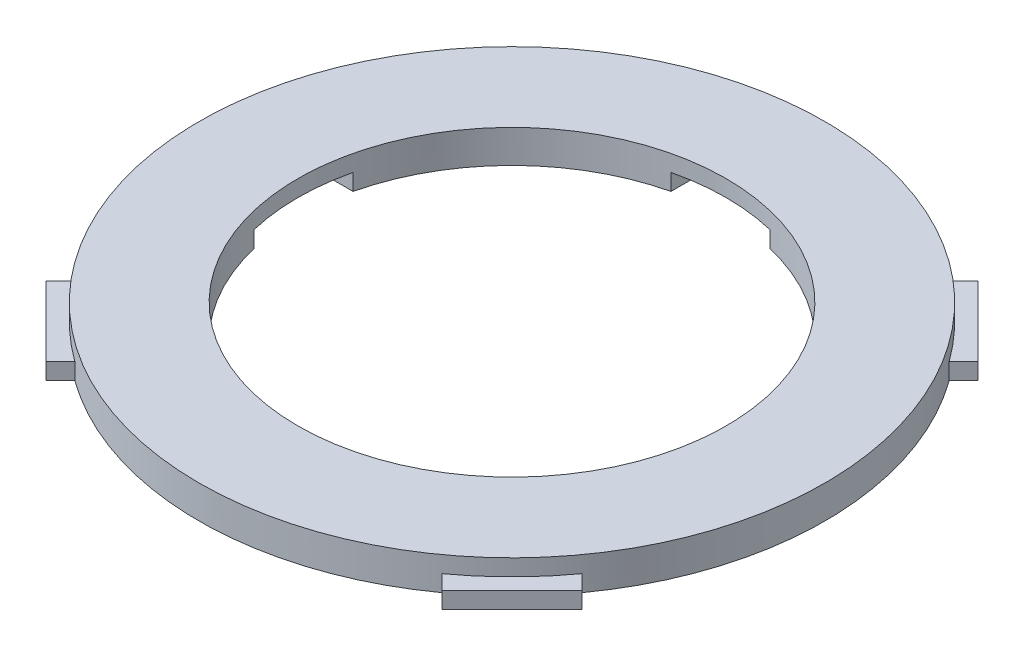
SolidWorks part; units mm, degrees
ref_plane "Front Plane" through (0, 0, 0) normal (0, 0, 1) x (1, 0, 0)
ref_plane "Top Plane" through (0, 0, 0) normal (0, 1, 0) x (1, 0, 0)
ref_plane "Right Plane" through (0, 0, 0) normal (1, 0, 0) x (0, 0, -1)
sketch "Sketch1" plane through (0, 0, 0) normal (0, 1, 0) x (1, 0, 0)
  line L0 (-67.1751, -67.1751) -> (67.1751, 67.1751) construction
  line L1 (-95, 0) -> (95, 0) construction
  line L2 (-67.1751, 67.1751) -> (67.1751, -67.1751) construction
  line L3 (0, 95) -> (0, -95) construction
  line L4 (67.1751, 67.1751) -> (-67.1751, -67.1751) construction
  line L5 (95, 0) -> (-95, 0) construction
  line L6 (67.1751, -67.1751) -> (-67.1751, 67.1751) construction
  line L7 (0, -95) -> (0, 95) construction
  line L8 (67.1751, 67.1751) -> (70.7107, 70.7107) construction
  line L9 (60.1041, 81.3173) -> (81.3173, 60.1041)
  line L10 (60.1041, 81.3173) -> (55.7259, 76.9391)
  line L11 (81.3173, 60.1041) -> (76.9391, 55.7259)
  line L12 (81.3173, -60.1041) -> (76.9391, -55.7259)
  line L13 (81.3173, -60.1041) -> (60.1041, -81.3173)
  line L14 (60.1041, -81.3173) -> (55.7259, -76.9391)
  line L15 (-60.1041, -81.3173) -> (-55.7259, -76.9391)
  line L16 (-60.1041, -81.3173) -> (-81.3173, -60.1041)
  line L17 (-81.3173, -60.1041) -> (-76.9391, -55.7259)
  line L18 (-81.3173, 60.1041) -> (-76.9391, 55.7259)
  line L19 (-81.3173, 60.1041) -> (-60.1041, 81.3173)
  line L20 (-60.1041, 81.3173) -> (-55.7259, 76.9391)
  line L21 (-70, -15) -> (-70, 15)
  line L22 (-70, 15) -> (-63.2456, 15)
  line L23 (-70, -15) -> (-63.2456, -15)
  line L24 (15, 70) -> (15, 63.2456)
  line L25 (-15, 70) -> (15, 70)
  line L26 (-15, 70) -> (-15, 63.2456)
  line L27 (70, -15) -> (63.2456, -15)
  line L28 (70, 15) -> (70, -15)
  line L29 (70, 15) -> (63.2456, 15)
  line L30 (-15, -70) -> (-15, -63.2456)
  line L31 (15, -70) -> (-15, -70)
  line L32 (15, -70) -> (15, -63.2456)
  circle A0 centre (0, 0) radius 65
  circle A1 centre (0, 0) radius 95
  point P7 (0, 0)
  point P10 (0, 0)
  point P25 (0, 0)
  point P27 (70.7107, 70.7107)
  point P29 (-65, 0)
  point P44 (0, 0)
  point P46 (-70, 0)
  point P47 (0, 0)
  point P63 (0, 0)
  dimension "D1" = 130
  dimension "D2" = 190
  dimension "D3" = 45
  dimension "D5" = 5
  dimension "D6" = 30
  dimension "D7" = 180
  dimension "D8" = 90
  dimension "D10" = 30
  dimension "D11" = 5
  dimension "D4" = 4
  dimension "D9" = 4
  dimension "D12" = 4
extrude "Boss-Extrude1" add sketch "Sketch1" along normal blind 10 contours A1 A0 L32 L31 L30 L23 L21 L22 L26 L25 L24 L29 L28 L27 region at (65.2751, 0, -65.2751)
extrude "Boss-Extrude2" add sketch "Sketch1<3>" along normal blind 5 contours A1 L20 L19 L18 | A1 L11 L9 L10 | A1 L14 L13 L12 | A1 L17 L16 L15 region at (68.7946, 0, -68.7946) region at (-68.7946, 0, -68.7946) region at (68.7946, 0, 68.7946) region at (-68.7946, 0, 68.7946)
sketch "Sketch1<3>" plane through (0, 0, 0) normal (0, 1, 0) x (1, 0, 0) same geometry as "Sketch1"
extrude "Boss-Extrude3" add sketch "Sketch1<4>" along normal blind 5 from offset 5 contours A0 L22 L21 L23 | A0 L30 L31 L32 | A0 L24 L25 L26 | A0 L27 L28 L29 region at (-67.1848, 0, 0) region at (0, 0, 67.1848) region at (0, 0, -67.1848) region at (67.1848, 0, 0)
sketch "Sketch1<4>" plane through (0, 0, 0) normal (0, 1, 0) x (1, 0, 0) same geometry as "Sketch1"
